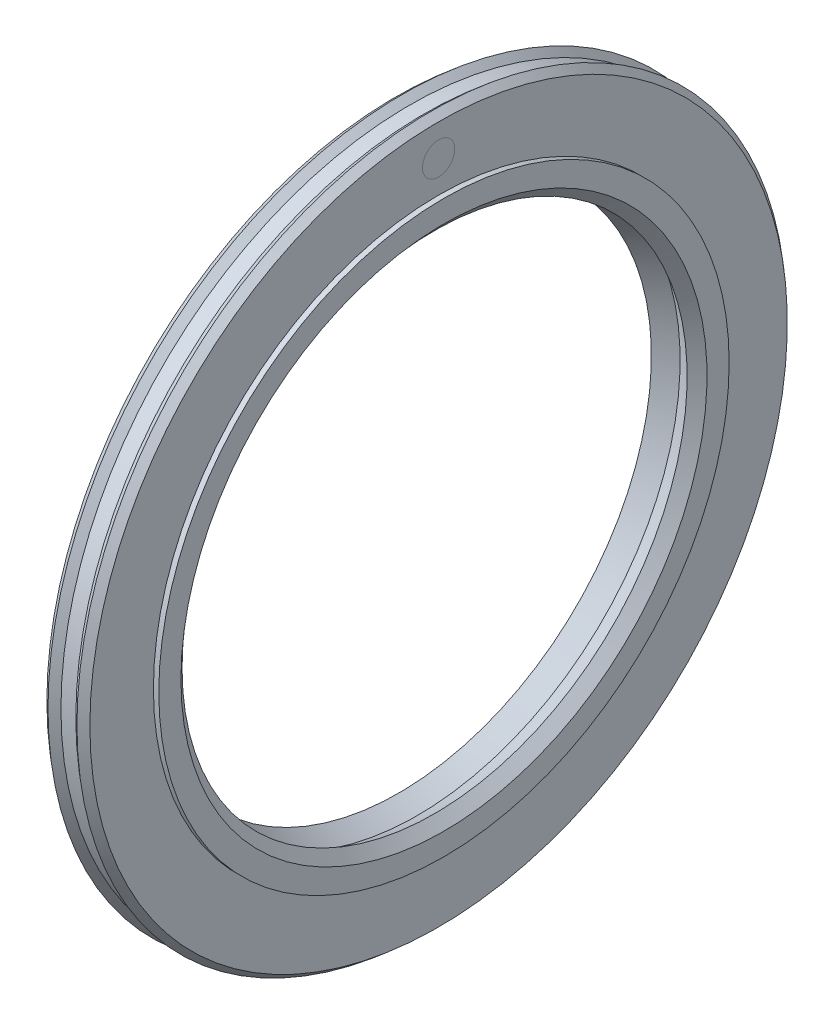
SolidWorks part; units mm, degrees
note: '?' marks a value the reader was unsure of.
ref_plane "Face" through (0, 0, 0) normal (0, 0, 1) x (1, 0, 0)
ref_plane "Dessus" through (0, 0, 0) normal (0, 1, 0) x (1, 0, 0)
ref_plane "Droite" through (0, 0, 0) normal (1, 0, 0) x (0, 0, -1)
sketch "Esquisse1" plane through (0, 0, 0) normal (0, 0, 1) x (1, 0, 0)
  line L0 (0, 32.4497) -> (0.6538, 33)
  line L1 (2.6924, 32.4497) -> (3.3462, 33)
  line L2 (0, 32.4497) -> (0, 26.5371)
  line L3 (0, 0) -> (8.5107, 0) construction
  line L4 (4, 32.4497) -> (4, 26.5371)
  line L5 (1.3076, 32.4497) -> (2.6924, 32.4497)
  line L6 (1.3076, 32.4497) -> (0.6538, 33)
  line L7 (4, 32.4497) -> (3.3462, 33)
  line L8 (4, 26.5371) -> (4.5, 26.5371)
  line L9 (4.5, 26.5371) -> (4.5, 24.4758)
  line L10 (2, 33) -> (2, 28.0419) construction
  line L11 (0, 26.5371) -> (0.5, 26.5371)
  line L12 (0.5, 26.5371) -> (0.5, 24.7934)
  line L13 (0.5, 24.7934) -> (0.3, 23.5)
  line L14 (0.3, 23.5) -> (2, 24.4758)
  line L15 (2, 24.4758) -> (3.6277, 23.5)
  line L16 (3.6277, 23.5) -> (4.5, 24.4758)
  point P9 (2, 32.4497)
  dimension "D1" = 0.5
  dimension "D2" = 4
  dimension "D4" = 4
  dimension "D5" = 0.2
revolve "Base-Révolution" add sketch "Esquisse1" angle 360 about L3
sketch "Esquisse2" plane through (0, 0, 0) normal (-1, 0, 0) x (0, 0, 1)
  circle A0 centre (0, 29.5) radius 1
  dimension "D1" = 29.5
extrude "Enlèv. mat.-Extru.1" cut sketch "Esquisse2" against normal blind 0.5
sketch "Esquisse3" plane through (4, 0, 0) normal (1, 0, 0) x (0, 0, -1)
  circle A0 centre (0, 29.4907) radius 1.5
split line "Ligne de séparation1"
ref_axis "Axe1" through (-2.3625, 0, 0) along (1, 0, 0)?
pattern_circular "Répétition circulaire1" count 6 over 360 about axis through (-2.3625, 0, 0) along (1, 0, 0)
sketch "Esquisse5" plane through (0, 0, 0) normal (-1, 0, 0) x (0, 0, 1)
  line L0 (0, 0) -> (39.4542, 0) construction
  circle A0 centre (31, 0) radius 0.5
  circle A1 centre (28, 0) radius 0.5
  dimension "D1" = 3
  dimension "D2" = 28
extrude "Enlèv. mat.-Extru.2" cut sketch "Esquisse5" against normal blind 0.5
